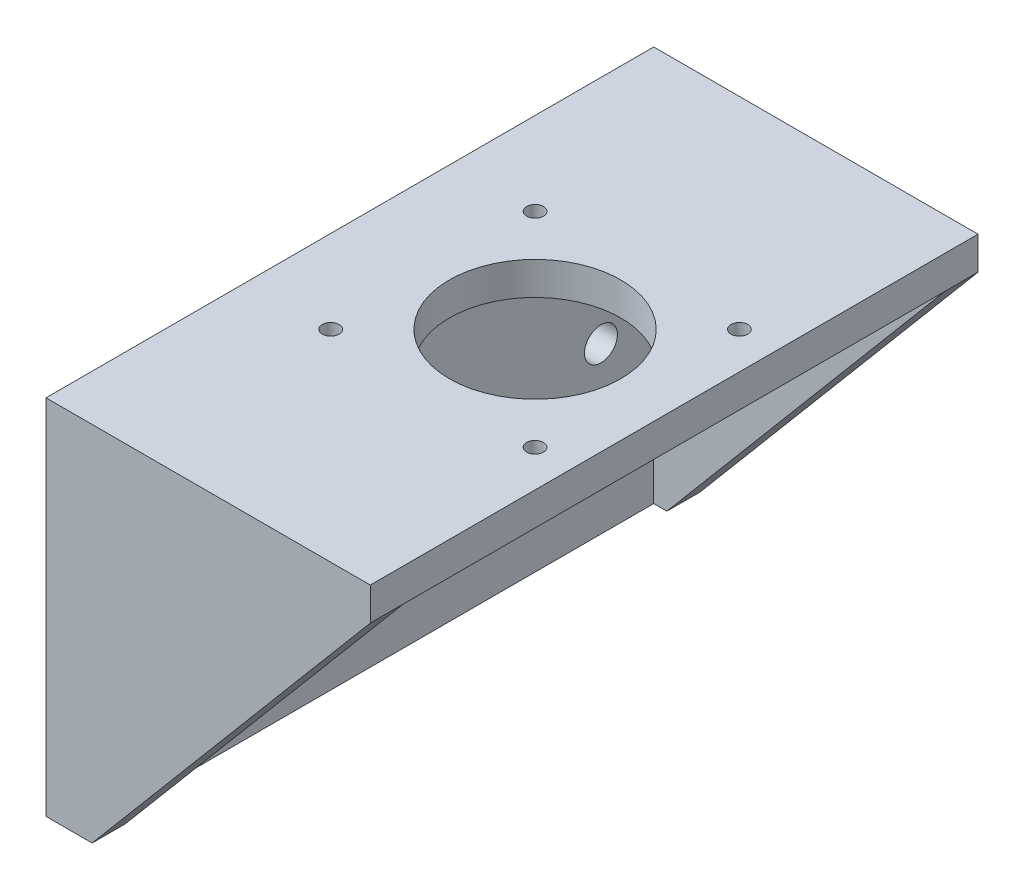
SolidWorks part; units mm, degrees
ref_plane "Front Plane" through (0, 0, 0) normal (0, 0, 1) x (1, 0, 0)
ref_plane "Top Plane" through (0, 0, 0) normal (0, 1, 0) x (1, 0, 0)
ref_plane "Right Plane" through (0, 0, 0) normal (1, 0, 0) x (0, 0, -1)
sketch "Sketch1" plane through (0, 0, 0) normal (0, 1, 0) x (1, 0, 0)
  line L0 (-21.1, 17.101) -> (-21.1, -17.101)
  line L2 (-17.101, -21.1) -> (17.101, -21.1)
  line L4 (21.1, -17.101) -> (21.1, 17.101)
  line L9 (21.1, -21.1) -> (-21.1, -21.1)
  line L10 (21.1, -21.1) -> (21.1, 21.1)
  line L12 (-21.1, -21.1) -> (-21.1, 21.1)
  line L13 (21.1, -21.1) -> (-21.1, 21.1) construction
  line L14 (21.1, 21.1) -> (-21.1, -21.1) construction
  line L23 (-21.1, -21.1) -> (21.1, -21.1)
  line L24 (-21.1, -21.1) -> (-21.1, -41.1)
  line L25 (-21.1, -41.1) -> (21.1, -41.1)
  line L26 (21.1, -21.1) -> (21.1, -41.1)
  line L27 (-21.1, -41.1) -> (21.1, -41.1)
  line L28 (-21.1, -41.1) -> (-21.1, -46.1)
  line L29 (-21.1, -46.1) -> (21.1, -46.1)
  line L30 (21.1, -41.1) -> (21.1, -46.1)
  line L31 (-21.1, 21.1) -> (21.1, 21.1)
  line L32 (-21.1, 21.1) -> (-21.1, 41.1)
  line L33 (-21.1, 41.1) -> (21.1, 41.1)
  line L34 (21.1, 21.1) -> (21.1, 41.1)
  line L35 (-21.1, 41.1) -> (21.1, 41.1)
  line L36 (-21.1, 41.1) -> (-21.1, 46.1)
  line L37 (-21.1, 46.1) -> (21.1, 46.1)
  line L38 (21.1, 41.1) -> (21.1, 46.1)
  line L39 (-21.1, 46.1) -> (-28.1, 46.1)
  line L40 (-21.1, 46.1) -> (-21.1, -46.1)
  line L41 (-21.1, -46.1) -> (-28.1, -46.1)
  line L42 (-28.1, 46.1) -> (-28.1, -46.1)
  circle A1 centre (15.5, -15.5) radius 1.275
  circle A2 centre (-15.5, -15.5) radius 1.275
  circle A3 centre (15.5, 15.5) radius 1.275
  circle A4 centre (-15.5, 15.5) radius 1.275
  circle A5 centre (0, 0) radius 13
  dimension "D1" = 20
  dimension "D2" = 5
extrude "Boss-Extrude3" add sketch "Sketch1" along normal blind 5 contours L33 L38 L37 L36 | L31 L34 L33 L32 | L39 L42 L41 L28 L24 L12 L0 L32 L36 | L31 L12 L0 L9 L2 L10 L4 A5 A4 A3 A2 A1 | L26 L9 L2 L24 L25 | L30 L25 L28 L29 region at (-20.5032, 0, -19.1005) region at (-24.6, 0, 0) region at (0, 0, -31.1) region at (0, 0, 31.1) region at (0, 0, -43.6) region at (0, 0, 43.6)
extrude "Boss-Extrude4" add sketch "Sketch1<3>" against normal blind 50 contours L39 L42 L41 L28 L24 L12 L0 L32 L36 | L30 L25 L28 L29 | L33 L38 L37 L36 region at (-24.6, 0, 0) region at (0, 0, -43.6) region at (0, 0, 43.6)
sketch "Sketch1<3>" plane through (0, 0, 0) normal (0, 1, 0) x (1, 0, 0) same geometry as "Sketch1"
sketch "Sketch2" plane through (0, 0, 46.1) normal (0, 0, 1) x (1, 0, 0)
  line L0 (-28.1, -50) -> (-21.1, -50)
  line L1 (21.1, -50) -> (-28.1, -50) construction
  line L2 (21.1, 5) -> (21.1, 0)
  line L3 (21.1, 5) -> (21.1, -50) construction
  line L4 (21.1, 0) -> (-21.1, -50)
  line L6 (21.1, -50) -> (-28.1, -50)
  line L7 (21.1, -50) -> (21.1, 5)
  line L8 (21.1, 5) -> (-28.1, 5)
  line L9 (-28.1, -50) -> (-28.1, 5)
  line M7 (-28.1, -50) -> (21.1, -50)
  line M8 (21.1, -50) -> (21.1, 5)
extrude "Cut-Extrude1" cut sketch "Sketch2" against normal through all contours L4 M8 M7 region at (7.0333, -33.3333, 46.1)
sketch "Sketch3" plane through (-21.1, 0, 0) normal (1, 0, 0) x (0, 0, -1)
  line L0 (-41.1, -50) -> (-41.1, 0)
  line L1 (-33.1, -25) -> (-41.1, -25)
  line L3 (0, -50) -> (0, -45.0415)
  line L4 (41.1, -50) -> (-41.1, -50) construction
  circle A0 centre (-33.1, -25) radius 2.5
  circle A1 centre (33.1, -25) radius 2.5
extrude "Cut-Extrude2" cut sketch "Sketch3" against normal through all contours A0 | A1 region at (-21.1, -27.4293, 33.1)
sketch "Sketch5" plane through (-21.1, 0, 0) normal (1, 0, 0) x (0, 0, -1)
  line L4 (41.1, 0) -> (-41.1, 0)
  line L5 (-41.1, 0) -> (-41.1, -50)
  line L6 (-41.1, -50) -> (41.1, -50)
  line L7 (41.1, -50) -> (41.1, 0)
  line L8 (41.1, 0) -> (-41.1, 0)
  line L9 (-41.1, 0) -> (-41.1, -50)
  line L10 (-41.1, -50) -> (41.1, -50)
  line L11 (41.1, -50) -> (41.1, 0)
  circle A0 centre (33.1, -25) radius 2.5 construction
  circle A1 centre (-33.1, -25) radius 2.5 construction
  circle A2 centre (33.1, -25) radius 2.5
  circle A3 centre (-33.1, -25) radius 2.5
  dimension "D1" = 0
extrude "Cut-Extrude3" cut sketch "Sketch5" against normal blind 2
